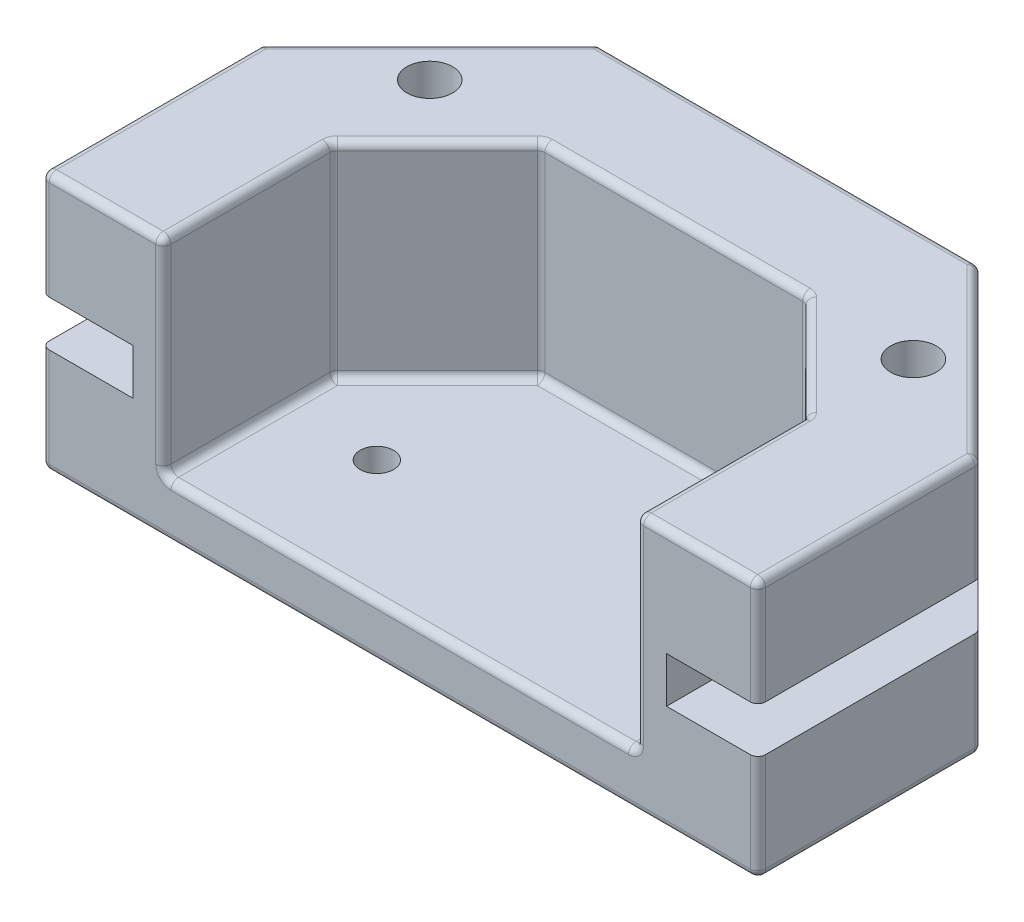
SolidWorks part; units mm, degrees
ref_plane "Front Plane" through (0, 0, 0) normal (0, 0, 1) x (1, 0, 0)
ref_plane "Top Plane" through (0, 0, 0) normal (0, 1, 0) x (1, 0, 0)
ref_plane "Right Plane" through (0, 0, 0) normal (1, 0, 0) x (0, 0, -1)
ref_plane "Motor Holder Bottom" through (0, -3.5, 0) normal (0, -1, 0) x (-1, 0, 0)
sketch "Sketch1" plane through (0, 0, 0) normal (0, 1, 0) x (1, 0, 0)
  line L7 (27.4734, -52.5) -> (21.4734, -52.5)
  line L13 (29.4734, -52.5) -> (60.5266, -52.5)
  line L16 (27.4734, -52.5) -> (27.4734, -40.5266)
  line L18 (60.5266, -52.5) -> (62.5266, -52.5)
  line L19 (55, -33) -> (62.5266, -40.5266)
  line L20 (27.4734, -40.5266) -> (35, -33)
  line L21 (62.5266, -40.5266) -> (62.5266, -52.5)
  line L22 (35, -33) -> (55, -33)
  line L23 (29.4734, -52.5) -> (29.4734, -41.3551)
  line L25 (29.4734, -41.3551) -> (36.3284, -34.5)
  line L26 (36.3284, -34.5) -> (53.6716, -34.5)
  line L27 (53.6716, -34.5) -> (60.5266, -41.3551)
  line L28 (60.5266, -41.3551) -> (60.5266, -52.5)
  line L30 (29.4734, -52.5) -> (27.4734, -52.5)
  line L31 (21.4734, -52.5) -> (21.4734, -38.0413)
  line L32 (21.4734, -38.0413) -> (32.5147, -27)
  line L33 (32.5147, -27) -> (57.4853, -27)
  line L34 (57.4853, -27) -> (68.5266, -38.0413)
  line L35 (68.5266, -38.0413) -> (68.5266, -52.5)
  line L36 (62.5266, -52.5) -> (68.5266, -52.5)
  line L37 (35, -33) -> (55, -33) construction
  line L38 (55, -33) -> (62.5266, -40.5266) construction
  line L39 (62.5266, -40.5266) -> (62.5266, -52.5) construction
  line L40 (35, -33) -> (27.4734, -40.5266) construction
  line L41 (27.4734, -40.5266) -> (27.4734, -52.5) construction
  line L42 (19.9734, -52.5) -> (27.4734, -52.5) construction
  dimension "D1" = 6
  dimension "D4" = 2
  dimension "D5" = 2
  dimension "D6" = 1.5
  dimension "D7" = 2
  dimension "D8" = 2
extrude "Boss-Extrude1" add sketch "Sketch1" along normal blind 10 and the other way blind 7 contours L16 | L16 L18 region at (24.4734, 0, 51.9648) region at (27.8745, 0, 46.5133)
extrude "Boss-Extrude4" add sketch "Sketch1<5>" along normal up to surface (-3.5 mm away) from surface contours L28 L27 L26 L25 L23 L13 region at (45, 0, 44.1163) up to plane "Motor Holder Bottom" starting at face at (45, -7, 40.9827)
sketch "Sketch1<5>" plane through (0, 0, 0) normal (0, 1, 0) x (1, 0, 0) same geometry as "Sketch1"
fillet "Fillet1" radius 0.5 36 edges at (29.4734, 10, 46.9275) (60.5266, 10, 46.9275) (60.5266, -3.5, 46.9275) (29.4734, -3.5, 46.9275) (45, -7, 52.5) (21.4734, 1.5, 52.5) (25.4734, 10, 52.5) (29.4734, 3.25, 52.5) (45, -3.5, 52.5) (60.5266, 3.25, 52.5) (64.5266, 10, 52.5) (68.5266, 1.5, 52.5) (57.0991, 10, 37.9275) (60.5266, 3.25, 41.3551) (57.0991, -3.5, 37.9275) (45, 10, 34.5) (53.6716, 3.25, 34.5) (45, -3.5, 34.5) (32.9009, 10, 37.9275) (36.3284, 3.25, 34.5) (32.9009, -3.5, 37.9275) (29.4734, 3.25, 41.3551) (21.4734, 10, 45.2707) (68.5266, 10, 45.2707) (63.006, 10, 32.5207) (45, 10, 27) (26.994, 10, 32.5207) (21.4734, 1.5, 38.0413) (32.5147, 1.5, 27) (57.4853, 1.5, 27) (68.5266, 1.5, 38.0413) (26.994, -7, 32.5207) (21.4734, -7, 45.2707) (45, -7, 27) (63.006, -7, 32.5207) (68.5266, -7, 45.2707)
extrude "Cut-Extrude1" cut sketch "Sketch1<3>" along normal up to surface (3 mm away) contours L16 region at (24.4734, 0, 51.9648)
sketch "Sketch1<3>" plane through (0, 0, 0) normal (0, 1, 0) x (1, 0, 0) same geometry as "Sketch1"
sketch "Sketch2" plane through (0, 10, 0) normal (0, 1, 0) x (1, 0, 0)
  line L0 (26.994, -32.5207) -> (31.2367, -36.7633) construction
  line L1 (21.4734, -38.0413) -> (32.5147, -27) construction
  line L3 (63.006, -32.5207) -> (58.7633, -36.7633) construction
  line L4 (57.4853, -27) -> (68.5266, -38.0413) construction
  line L6 (35, -33) -> (27.4734, -40.5266) construction
  line L7 (55, -33) -> (62.5266, -40.5266) construction
  circle A0 centre (29.1154, -34.642) radius 1.5
  circle A1 centre (60.8846, -34.642) radius 1.5
  dimension "D1" = 3
  dimension "D2" = 3
extrude "Cut-Extrude2" cut sketch "Sketch2" against normal up to surface (17 mm away) up to face at (45, -7, 39.2495)
sketch "Sketch4" plane through (0, 0, 0) normal (0, 1, 0) x (1, 0, 0)
  circle A0 centre (35.5, -44.5) radius 1.1 construction
  circle A1 centre (35.5, -44.5) radius 1.1
  circle A2 centre (54.5, -44.5) radius 1.1 construction
  circle A3 centre (54.5, -44.5) radius 1.1
extrude "Cut-Extrude3" cut sketch "Sketch4" against normal up to surface (7 mm away) from surface up to face at (29.1154, -7, 36.142) starting at face at (45, -3.5, 42.8541)
